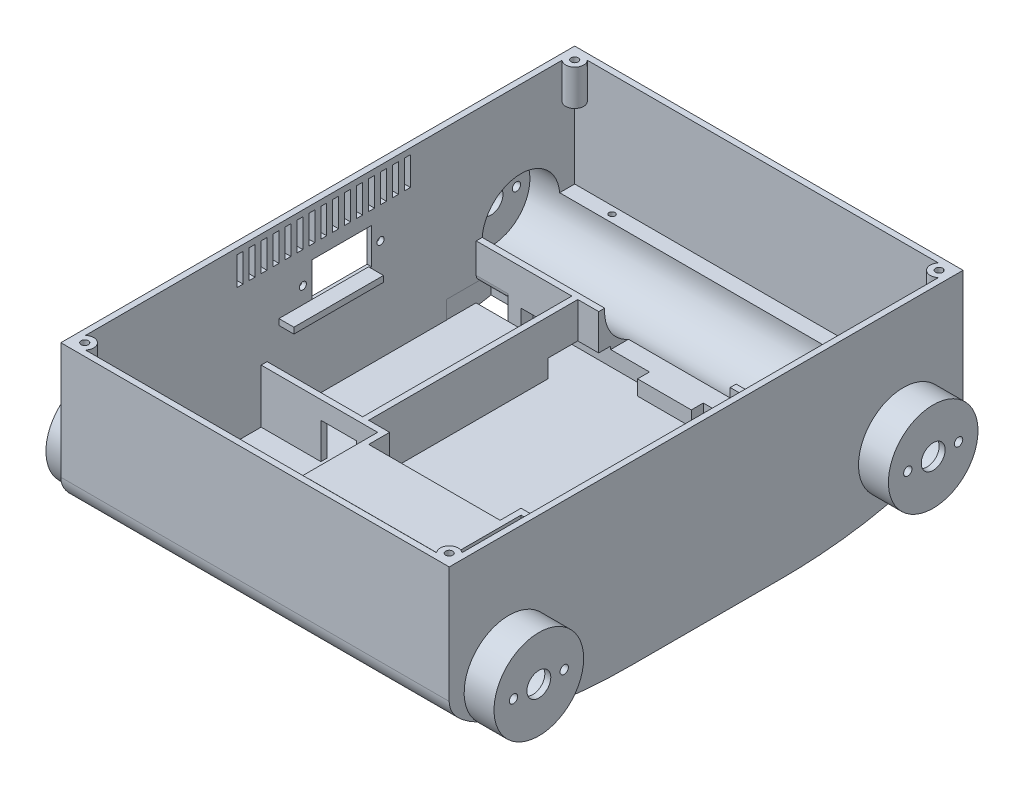
SolidWorks part; units mm, degrees
ref_plane "Спереди" through (0, 0, 0) normal (0, 0, 1) x (1, 0, 0)
ref_plane "Сверху" through (0, 0, 0) normal (0, 1, 0) x (1, 0, 0)
ref_plane "Справа" through (0, 0, 0) normal (1, 0, 0) x (0, 0, -1)
sketch "Эскиз1" plane through (0, 0, 0) normal (0, 1, 0) x (1, 0, 0)
  line L1 (-65, 86) -> (65, 86)
  line L2 (-65, 86) -> (-65, -86)
  line L3 (-65, -86) -> (65, -86)
  line L4 (65, 86) -> (65, -86)
  dimension "D1" = 130
  dimension "D2" = 65
  dimension "D3" = 172
  dimension "D4" = 86
extrude "Бобышка-Вытянуть1" add sketch "Эскиз1" along normal blind 35 and the other way blind 35
sketch "Эскиз2" plane through (65, 0, 0) normal (1, 0, 0) x (0, 0, -1)
  line L0 (-86, -15) -> (86, -15) construction
  line L1 (-86, -35) -> (-86, 35) construction
  line L2 (86, -35) -> (86, 35) construction
  line L3 (-86, -35) -> (86, -35) construction
  line L4 (-25, -35) -> (25, -35)
  line L5 (-86, -40.7424) -> (-86, -15)
  line L7 (-86, -40.7424) -> (86, -40.7424)
  line L8 (86, -40.7424) -> (86, -15)
  ellipse E0 centre (-25, -15) end of major axis (-86, -15) minor radius 20 (-86, -15) -> (-25, -35) ccw
  ellipse E1 centre (25, -15) end of major axis (-36, -15) minor radius 20 (86, -15) -> (25, -35) cw
  point P10 (-25, -15)
  point P11 (25, -15)
  dimension "D1" = 20
  dimension "D2" = 50
  dimension "D3" = 25
  dimension "D4" = 25
  dimension "D5" = 25
extrude "Вырез-Вытянуть1" cut sketch "Эскиз2" against normal blind 130
sketch "Эскиз3" plane through (0, 35, 0) normal (0, 1, 0) x (1, 0, 0)
  line L0 (-65, 86) -> (-65, -86) construction
  line L1 (-63, 84) -> (63, 84)
  line L2 (-63, 84) -> (-63, -84)
  line L3 (-63, -84) -> (63, -84)
  line L4 (63, 84) -> (63, -84)
  line L5 (65, -86) -> (65, 86) construction
  line L6 (-65, -86) -> (65, -86) construction
  line L7 (65, 86) -> (-65, 86) construction
  dimension "D1" = 2
  dimension "D2" = 2
  dimension "D3" = 2
  dimension "D4" = 2
extrude "Вырез-Вытянуть2" cut sketch "Эскиз3" against normal blind 49
sketch "Эскиз4" plane through (0, 0, 0) normal (1, 0, 0) x (0, 0, -1)
  line L0 (-86, -15) -> (86, -15) construction
  circle A0 centre (-66, -15) radius 13
  circle A1 centre (66, -15) radius 13
  ellipse E0 centre (25, -15) end of major axis (86, -15) minor radius 20 (25, -35) -> (86, -15) ccw construction
  point P10 (-66, -15)
  point P11 (66, -15)
  dimension "D3" = 26
  dimension "D4" = 26
  dimension "D1" = 20
  dimension "D2" = 20
extrude "Вырез-Вытянуть3" cut sketch "Эскиз4" against normal blind 63 and the other way blind 63
sketch "Эскиз7" plane through (65, 0, 0) normal (1, 0, 0) x (0, 0, -1)
  line L0 (-86, -15) -> (86, -15) construction
  line L1 (-86, -15) -> (-86, 35) construction
  line L2 (86, -15) -> (86, 35) construction
  line L3 (-86, 35) -> (86, 35) construction
  circle A0 centre (-74.5, -15) radius 1.4
  circle A1 centre (-66, -15) radius 4
  circle A2 centre (-57.5, -15) radius 1.4
  circle A3 centre (57.5, -15) radius 1.4
  circle A4 centre (66, -15) radius 4
  circle A5 centre (74.5, -15) radius 1.4
  point P8 (-66, -15)
  point P9 (66, -15)
  point P10 (-74.5, -15)
  point P11 (-57.5, -15)
  point P12 (74.5, -15)
  point P13 (57.5, -15)
  dimension "D8" = 2.8
  dimension "D9" = 2.8
  dimension "D10" = 2.8
  dimension "D11" = 2.8
  dimension "D12" = 8
  dimension "D13" = 8
  dimension "D1" = 50
  dimension "D2" = 20
  dimension "D3" = 20
  dimension "D4" = 8.5
  dimension "D5" = 8.5
  dimension "D6" = 8.5
  dimension "D7" = 8.5
sketch "Эскиз8" plane through (65, 0, 0) normal (1, 0, 0) x (0, 0, -1)
  line L0 (-86, -15) -> (-86, 35) construction
  circle A0 centre (-66, -15) radius 15
  circle A1 centre (66, -15) radius 15
  dimension "D1" = 20
  dimension "D2" = 30
  dimension "D3" = 20
extrude "Бобышка-Вытянуть3" add sketch "Эскиз8" along normal blind 10
mirror "Зеркальное отражение2" about plane through (0, 0, 0) normal (1, 0, 0) of "Бобышка-Вытянуть3"
extrude "Вырез-Вытянуть6" cut sketch "Эскиз7" along normal blind 32 and the other way blind 160
sketch "Эскиз9" plane through (63, 0, 0) normal (-1, 0, 0) x (0, 0, 1)
  circle A0 centre (-66, -15) radius 13
  circle A1 centre (66, -15) radius 13
  dimension "D1" = 26
  dimension "D2" = 26
extrude "Вырез-Вытянуть7" cut sketch "Эскиз9" against normal blind 10 and the other way blind 136
sketch "Эскиз10" plane through (0, -14, 0) normal (0, 1, 0) x (1, 0, 0)
  line L1 (-63, 51.0385) -> (-31, 51.0385)
  line L2 (-63, 51.0385) -> (-63, -18.9615)
  line L3 (-63, -18.9615) -> (-31, -18.9615)
  line L4 (-31, 51.0385) -> (-31, -18.9615)
  line L7 (63, 53.0385) -> (-63, 53.0385) construction
  line L8 (-63, 53.0385) -> (-63, -53.0385) construction
  line L9 (63, -53.0385) -> (63, 53.0385) construction
  line L10 (31, 51.0385) -> (63, 51.0385)
  line L11 (31, 51.0385) -> (31, -18.9615)
  line L12 (31, -18.9615) -> (63, -18.9615)
  line L13 (63, 51.0385) -> (63, -18.9615)
  dimension "D1" = 70
  dimension "D2" = 2
  dimension "D3" = 2
  dimension "D4" = 32
  dimension "D5" = 0
  dimension "D6" = 70
  dimension "D7" = 32
  dimension "D8" = 0
extrude "Вырез-Вытянуть8" cut sketch "Эскиз10" against normal blind 18
sketch "Эскиз11" plane through (0, -14, 0) normal (0, 1, 0) x (1, 0, 0)
  line L0 (63, 53.0385) -> (-63, 53.0385) construction
  line L1 (-29, 51.0385) -> (29, 51.0385)
  line L2 (-29, 51.0385) -> (-29, -18.9615)
  line L3 (-29, -18.9615) -> (29, -18.9615)
  line L4 (29, 51.0385) -> (29, -18.9615)
  line L7 (-31, -18.9615) -> (-31, 51.0385) construction
  line L8 (31, 51.0385) -> (31, -18.9615) construction
  line L9 (-63, -18.9615) -> (-31, -18.9615) construction
  dimension "D1" = 2
  dimension "D2" = 0
  dimension "D3" = 2
  dimension "D4" = 2
  dimension "D5" = 58
  dimension "D6" = 70
extrude "Вырез-Вытянуть9" cut sketch "Эскиз11" against normal blind 18
sketch "Эскиз13" plane through (0, -14, 0) normal (0, 1, 0) x (1, 0, 0)
  line L0 (29, 51.0385) -> (-29, 51.0385) construction
  line L1 (-22, 51.0385) -> (22, 51.0385)
  line L2 (-22, 51.0385) -> (-22, 67.0385)
  line L3 (-22, 67.0385) -> (22, 67.0385)
  line L4 (22, 51.0385) -> (22, 67.0385)
  line L8 (-63, -53.0385) -> (63, -53.0385) construction
  line L9 (-29, -18.9615) -> (29, -18.9615) construction
  line L10 (-8, -25.9615) -> (-22, -25.9615)
  line L11 (-22, -18.9615) -> (-22, -25.9615)
  line L12 (-22, -18.9615) -> (22, -18.9615)
  line L14 (-22, -67.0385) -> (22, -67.0385)
  line L16 (22, -18.9615) -> (22, -25.9615)
  line L17 (-8, -25.9615) -> (-8, -45.9615)
  line L18 (8, -25.9615) -> (8, -45.9615)
  line L19 (22, -67.0385) -> (22, -45.9615)
  line L20 (-22, -67.0385) -> (-22, -45.9615)
  line L21 (-8, -45.9615) -> (-22, -45.9615)
  line L22 (8, -25.9615) -> (22, -25.9615)
  line L23 (8, -45.9615) -> (22, -45.9615)
  dimension "D1" = 44
  dimension "D2" = 22
  dimension "D3" = 14
  dimension "D4" = 8
  dimension "D5" = 16
  dimension "D6" = 22
  dimension "D7" = 22
  dimension "D8" = 20
  dimension "D9" = 7
  dimension "D10" = 7.077
  dimension "D11" = 16
  dimension "D12" = 22
extrude "Вырез-Вытянуть11" cut sketch "Эскиз13" against normal blind 13
sketch "Эскиз14" plane through (0, 0, -51.0385) normal (0, 0, 1) x (1, 0, 0)
  line L0 (-63, -32) -> (-63, -14) construction
  line L1 (-9, -26) -> (-48, -26)
  line L2 (-9, -26) -> (-9, -32)
  line L3 (-9, -32) -> (-48, -32)
  line L4 (-48, -26) -> (-48, -32)
  line L5 (-29, -32) -> (-29, -14) construction
  line L6 (29, -32) -> (-29, -32) construction
  line L7 (-31, -32) -> (-31, -14) construction
  line L9 (-63.0555, -32) -> (-52.3555, -32)
  line L10 (-63.0555, -32) -> (-63.0555, -26)
  line L11 (-63.0555, -26) -> (-52.3555, -26)
  line L12 (-52.3555, -32) -> (-52.3555, -26)
  dimension "D1" = 15
  dimension "D2" = 20
  dimension "D3" = 6
  dimension "D4" = 0
  dimension "D5" = 17
  dimension "D6" = 10.7
  dimension "D7" = 6
extrude "Вырез-Вытянуть12" cut sketch "Эскиз14" against normal blind 4 and the other way blind 10
mirror "Зеркальное отражение4" about plane through (0, 0, 0) normal (1, 0, 0) of "Вырез-Вытянуть12"
sketch "Эскиз15" plane through (63, 0, 0) normal (-1, 0, 0) x (0, 0, 1)
  line L0 (18.9615, -14) -> (-51.0385, -14) construction
  line L1 (-15, -3.5) -> (15, -3.5)
  line L2 (-15, -3.5) -> (-15, -5.5)
  line L3 (-15, -5.5) -> (15, -5.5)
  line L4 (15, -3.5) -> (15, -5.5)
  dimension "D1" = 30
  dimension "D2" = 15
  dimension "D3" = 2
  dimension "D4" = 8.5
extrude "Бобышка-Вытянуть4" add sketch "Эскиз15" along normal blind 5
mirror "Зеркальное отражение3" about plane through (0, 0, 0) normal (1, 0, 0) of "Бобышка-Вытянуть4"
sketch "Эскиз16" plane through (0, -14, 0) normal (0, 1, 0) x (1, 0, 0)
  line L0 (-63, 78.9615) -> (63, 78.9615) construction
  line L1 (-63, 84) -> (-63, 78.9615) construction
  circle A0 centre (-48, 81.5015) radius 1
  point P6 (-63, 81.4807)
  dimension "D1" = 2.54
  dimension "D3" = 2
  dimension "D2" = 15
extrude "Вырез-Вытянуть13" cut sketch "Эскиз16" against normal blind 5
mirror "Зеркальное отражение5" about plane through (0, 0, 0) normal (0, 0, 1) of "Вырез-Вытянуть13"
mirror "Зеркальное отражение6" about plane through (0, 0, 0) normal (1, 0, 0) of "Зеркальное отражение5"
sketch "Эскиз17" plane through (0, -32, 0) normal (0, 1, 0) x (1, 0, 0)
  line L1 (-52.3555, 51.0385) -> (-63.0555, 51.0385)
  line L2 (-52.3555, 51.0385) -> (-52.3555, 56.0385)
  line L3 (-52.3555, 56.0385) -> (-63.0555, 56.0385)
  line L4 (-63.0555, 51.0385) -> (-63.0555, 56.0385)
  dimension "D1" = 5
extrude "Вырез-Вытянуть14" cut sketch "Эскиз17" against normal through all and the other way blind 3
mirror "Зеркальное отражение10" about plane through (0, 0, 0) normal (1, 0, 0) of "Вырез-Вытянуть14"
fillet "Скругление17" radius 2 4 edges at (-57.7055, -29, -55.0385) (-57.6778, -26, -51.0385) (57.6778, -26, -51.0385) (57.7055, -29, -55.0385)
sketch "Эскиз18" plane through (0, -14, 0) normal (0, 1, 0) x (1, 0, 0)
  line L1 (-8, -25.9615) -> (8, -25.9615)
  line L2 (-8, -25.9615) -> (-8, -45.9615)
  line L3 (-8, -45.9615) -> (8, -45.9615)
  line L4 (8, -25.9615) -> (8, -45.9615)
extrude "Бобышка-Вытянуть5" add sketch "Эскиз18" against normal blind 2
sketch "Эскиз19" plane through (0, -14, 0) normal (0, 1, 0) x (1, 0, 0)
  line L0 (-63, 84) -> (-63, -84) construction
  line L1 (-63, -20.9615) -> (-24, -20.9615)
  line L2 (-63, -20.9615) -> (-63, -51.0385)
  line L3 (-63, -51.0385) -> (-24, -51.0385)
  line L4 (-24, -20.9615) -> (-24, -51.0385)
  line L5 (24, -20.9615) -> (63, -20.9615)
  line L6 (24, -20.9615) -> (24, -51.0385)
  line L7 (24, -51.0385) -> (63, -51.0385)
  line L8 (63, -20.9615) -> (63, -51.0385)
  line L9 (-63, -18.9615) -> (-31, -18.9615) construction
  line L10 (-63, -53.0385) -> (-22, -53.0385) construction
  line L11 (-22, -45.9615) -> (-22, -61) construction
  line L12 (22, -53.0385) -> (22, -45.9615) construction
  line L13 (-29, -18.9615) -> (29, -18.9615) construction
  line L14 (22, -53.0385) -> (63, -53.0385) construction
  line L15 (63, -84) -> (63, 84) construction
  dimension "D1" = 0
  dimension "D2" = 2
  dimension "D3" = 2
  dimension "D4" = 2
  dimension "D5" = 2
  dimension "D6" = 2
  dimension "D7" = 2
  dimension "D8" = 0
extrude "Вырез-Вытянуть15" cut sketch "Эскиз19" against normal blind 18
sketch "Эскиз20" plane through (0, -32, 0) normal (0, 1, 0) x (1, 0, 0)
  line L0 (-24, -20.9615) -> (-63, -20.9615) construction
  line L1 (-31, -18.9615) -> (-43, -18.9615)
  line L2 (-31, -18.9615) -> (-31, -20.9615)
  line L3 (-31, -20.9615) -> (-43, -20.9615)
  line L4 (-43, -18.9615) -> (-43, -20.9615)
  dimension "D1" = 12
extrude "Вырез-Вытянуть16" cut sketch "Эскиз20" along normal blind 12
sketch "Эскиз21" plane through (0, -32, 0) normal (0, 1, 0) x (1, 0, 0)
  line L0 (63, -20.9615) -> (24, -20.9615) construction
  line L1 (63, -18.9615) -> (51, -18.9615)
  line L2 (63, -18.9615) -> (63, -20.9615)
  line L3 (63, -20.9615) -> (51, -20.9615)
  line L4 (51, -18.9615) -> (51, -20.9615)
  dimension "D1" = 12
extrude "Вырез-Вытянуть17" cut sketch "Эскиз21" along normal blind 12
sketch "Эскиз22" plane through (0, 0, 18.9615) normal (0, 0, -1) x (-1, 0, 0)
  line L0 (29, -32) -> (-29, -32) construction
  line L1 (24, -20) -> (29, -20)
  line L2 (24, -20) -> (24, -32)
  line L3 (24, -32) -> (29, -32)
  line L4 (29, -20) -> (29, -32)
  line L5 (29, -32) -> (29, -14) construction
  line L6 (22, -27) -> (22, -14) construction
  line L7 (29, -14) -> (22, -14) construction
  dimension "D1" = 0
  dimension "D2" = 0
  dimension "D3" = 2
  dimension "D4" = 6
extrude "Вырез-Вытянуть18" cut sketch "Эскиз22" against normal blind 9
sketch "Эскиз24" plane through (-65, 0, 0) normal (-1, 0, 0) x (0, 0, 1)
  line L1 (-86, 35) -> (86, 35) construction
  line L2 (-86, -15) -> (-86, 35) construction
  line L3 (-25, 22) -> (-23, 22)
  line L4 (-25, 22) -> (-25, 12.5)
  line L7 (-25, 12.5) -> (-23, 12.5)
  line L8 (-29, 22) -> (-27, 22)
  line L9 (-29, 22) -> (-29, 12.5)
  line L10 (-29, 12.5) -> (-27, 12.5)
  line L11 (-27, 22) -> (-27, 12.5)
  line L12 (-23, 22) -> (-23, 12.5)
  line L13 (-21, 22) -> (-19, 22)
  line L14 (-21, 22) -> (-21, 12.5)
  line L15 (-21, 12.5) -> (-19, 12.5)
  line L16 (-19, 22) -> (-19, 12.5)
  line L17 (-17, 22) -> (-15, 22)
  line L18 (-17, 22) -> (-17, 12.5)
  line L19 (-17, 12.5) -> (-15, 12.5)
  line L20 (-15, 22) -> (-15, 12.5)
  line L21 (-13, 22) -> (-11, 22)
  line L22 (-13, 22) -> (-13, 12.5)
  line L23 (-13, 12.5) -> (-11, 12.5)
  line L24 (-11, 22) -> (-11, 12.5)
  line L25 (-9, 22) -> (-7, 22)
  line L26 (-9, 22) -> (-9, 12.5)
  line L27 (-9, 12.5) -> (-7, 12.5)
  line L28 (-7, 22) -> (-7, 12.5)
  line L29 (-5, 22) -> (-3, 22)
  line L30 (-5, 22) -> (-5, 12.5)
  line L31 (-5, 12.5) -> (-3, 12.5)
  line L32 (-3, 22) -> (-3, 12.5)
  line L33 (-1, 22) -> (1, 22)
  line L34 (-1, 22) -> (-1, 12.5)
  line L35 (-1, 12.5) -> (1, 12.5)
  line L36 (1, 22) -> (1, 12.5)
  line L37 (3, 22) -> (5, 22)
  line L38 (3, 22) -> (3, 12.5)
  line L39 (3, 12.5) -> (5, 12.5)
  line L40 (5, 22) -> (5, 12.5)
  line L41 (7, 22) -> (9, 22)
  line L42 (7, 22) -> (7, 12.5)
  line L43 (7, 12.5) -> (9, 12.5)
  line L44 (9, 22) -> (9, 12.5)
  line L45 (11, 22) -> (13, 22)
  line L46 (11, 22) -> (11, 12.5)
  line L47 (11, 12.5) -> (13, 12.5)
  line L48 (13, 22) -> (13, 12.5)
  line L49 (15, 22) -> (17, 22)
  line L50 (15, 22) -> (15, 12.5)
  line L51 (15, 12.5) -> (17, 12.5)
  line L52 (17, 22) -> (17, 12.5)
  line L53 (19, 22) -> (21, 22)
  line L54 (19, 22) -> (19, 12.5)
  line L55 (19, 12.5) -> (21, 12.5)
  line L56 (21, 22) -> (21, 12.5)
  line L57 (23, 22) -> (25, 22)
  line L58 (23, 22) -> (23, 12.5)
  line L59 (23, 12.5) -> (25, 12.5)
  line L60 (25, 22) -> (25, 12.5)
  line L61 (27, 22) -> (29, 22)
  line L62 (27, 22) -> (27, 12.5)
  line L63 (27, 12.5) -> (29, 12.5)
  line L64 (29, 22) -> (29, 12.5)
  line L65 (86, -15) -> (86, 35) construction
  dimension "D1" = 13
  dimension "D2" = 57
  dimension "D3" = 15
  dimension "D4" = 57
  dimension "D6" = 2
  dimension "D7" = 9.5
extrude "Вырез-Вытянуть19" cut sketch "Эскиз24" against normal blind 2
sketch "Эскиз25" plane through (-65, 0, 0) normal (-1, 0, 0) x (0, 0, 1)
  line L0 (-86, 35) -> (86, 35) construction
  line L1 (-16, 8) -> (4, 8)
  line L2 (-16, 8) -> (-16, -4)
  line L3 (-16, -4) -> (4, -4)
  line L4 (4, 8) -> (4, -4)
  line L5 (-86, -15) -> (-86, 35) construction
  circle A0 centre (7, 2) radius 1.2
  circle A1 centre (-19, 2) radius 1.2
  dimension "D7" = 2.4
  dimension "D8" = 2.4
  dimension "D1" = 20
  dimension "D2" = 12
  dimension "D3" = 27
  dimension "D4" = 70
  dimension "D5" = 6
  dimension "D6" = 6
  dimension "D9" = 3
  dimension "D10" = 3
extrude "Вырез-Вытянуть20" cut sketch "Эскиз25" against normal blind 2
sketch "Эскиз26" plane through (-65, 0, 0) normal (-1, 0, 0) x (0, 0, 1)
  line L0 (-16, 8) -> (-16, -4) construction
  line L1 (-22, 10) -> (10, 10)
  line L2 (-22, 10) -> (-22, -6)
  line L3 (-22, -6) -> (10, -6)
  line L4 (10, 10) -> (10, -6)
  line L5 (-16, -4) -> (4, -4) construction
  dimension "D1" = 32
  dimension "D2" = 16
  dimension "D3" = 6
  dimension "D4" = 2
extrude "Вырез-Вытянуть21" cut sketch "Эскиз26" against normal blind 0.5
sketch "Эскиз28" plane through (0, 35, 0) normal (0, 1, 0) x (1, 0, 0)
  line L1 (-91.6273, 97.3687) -> (88.3466, 97.3687)
  line L2 (-91.6273, 97.3687) -> (-91.6273, -97.8374)
  line L3 (-91.6273, -97.8374) -> (88.3466, -97.8374)
  line L4 (88.3466, 97.3687) -> (88.3466, -97.8374)
extrude "Вырез-Вытянуть22" cut sketch "Эскиз28" against normal blind 11
sketch "Эскиз29" plane through (0, 24, 0) normal (0, 1, 0) x (1, 0, 0)
  line L0 (-65, 86) -> (65, 86) construction
  line L1 (-65, -86) -> (-65, 86) construction
  circle A0 centre (-61, 82) radius 3
  circle A1 centre (-61, 82) radius 1.2
  dimension "D3" = 6
  dimension "D4" = 2.4
  dimension "D1" = 4
  dimension "D2" = 4
extrude "Бобышка-Вытянуть6" add sketch "Эскиз29" against normal blind 12
mirror "Зеркальное отражение11" about plane through (0, 0, 0) normal (0, 0, 1) of "Бобышка-Вытянуть6"
mirror "Зеркальное отражение12" about plane through (0, 0, 0) normal (1, 0, 0) of "Зеркальное отражение11"
